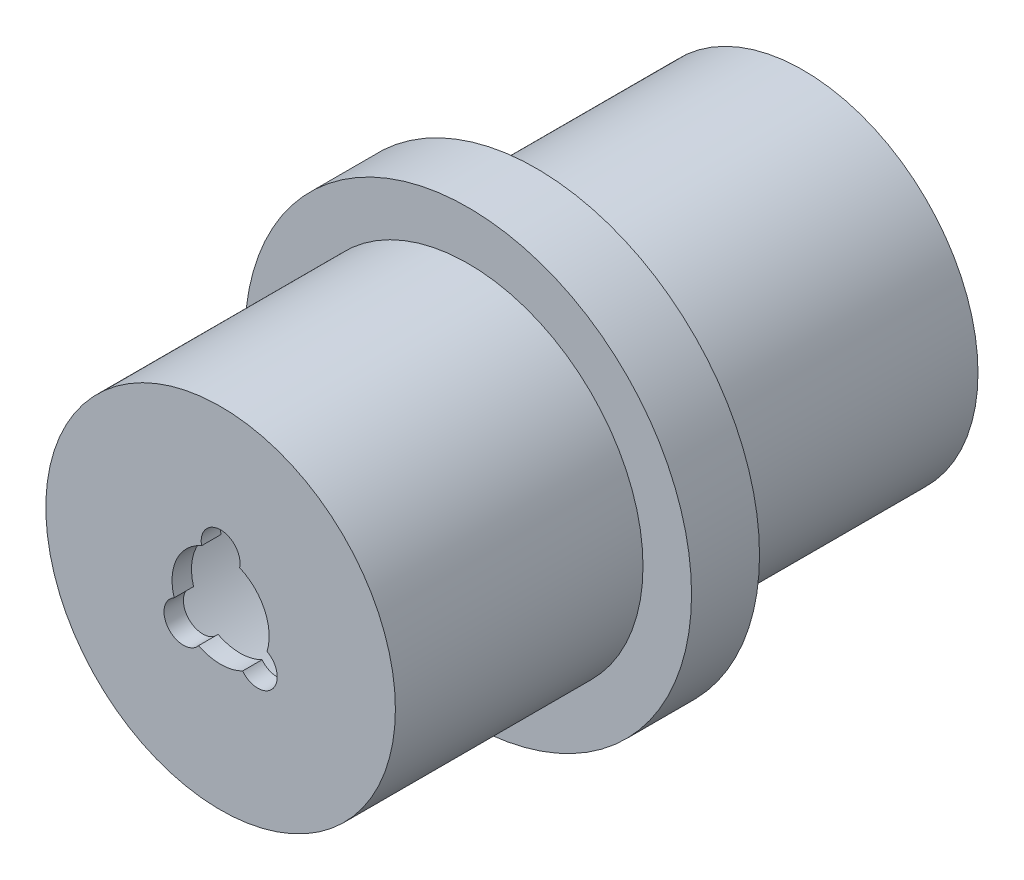
SolidWorks part; units mm, degrees
ref_plane "Front Plane" through (0, 0, 0) normal (0, 0, 1) x (1, 0, 0)
ref_plane "Top Plane" through (0, 0, 0) normal (0, 1, 0) x (1, 0, 0)
ref_plane "Right Plane" through (0, 0, 0) normal (1, 0, 0) x (0, 0, -1)
sketch "Sketch1" plane through (0, 0, 0) normal (1, 0, 0) x (0, 0, -1)
  line L0 (-60, 5) -> (-58, 5)
  line L1 (-60, 0) -> (0, 0)
  line L2 (-60, 0) -> (-60, 23)
  line L3 (-60, 23) -> (0, 23)
  line L4 (0, 0) -> (0, 23)
  line L5 (-1072.3815, 0) -> (1072.3815, 0) construction
  line L6 (-31, -974.342) -> (-31, 49025.6579)
  line L10 (-58, 0) -> (-2, 0)
  line L11 (-58, 0) -> (-58, 17)
  line L12 (-58, 17) -> (-2, 17)
  line L13 (-2, 0) -> (-2, 17)
  line L15 (-60, 18) -> (0, 18)
  line L16 (-27.5, 23) -> (-27.5, 18)
  line L17 (-2, 13) -> (0, 13)
  line L18 (-34.5, 23) -> (-34.5, 18)
  point P14 (-31, 17)
  dimension "D3" = 56
  dimension "D1" = 2
  dimension "D2" = 17
  dimension "D6" = 27
  dimension "D5" = 5
  dimension "D9" = 4
  dimension "D4" = 6
  dimension "D7" = 2
  dimension "D8" = 1
  dimension "D10" = 7
revolve "Revolve1" add sketch "Sketch1" angle 360 about L5 region at (0, 11.5, 59.6822) region at (0, 20.5, 32.75) region at (0, 17.5, 30.686) region at (0, 20.5, 29.25)
ref_axis "Axis1" through (0, 0, -68.4732) along (0, 0, 1)
ref_axis "Axis2" through (0, -974.342, 31) along (0, 1, 0)
ref_plane "Plane1" through (0, 0, 31) normal (0, 0, 1) x (1, 0, 0)
sketch "Sketch3" plane through (0, 0, 31) normal (0, 0, 1) x (1, 0, 0)
  line L0 (0, -999.5695) -> (0, 49000.4305) construction
  line L1 (-340.1578, -934.5758) -> (16760.8494, 46050.0552) construction
  line L2 (-1, 19.9725) -> (1, 19.9725)
  line L3 (338.8634, -931.0195) -> (-16762.1438, 46053.6116) construction
  line L4 (1, 19.9725) -> (4.5052, 16.5181) construction
  line L5 (0, 19.9725) -> (0, 23.1006) construction
  line L6 (2.0302, 19.9725) -> (-0.0328, 19.9725) construction
  line L7 (3.5107, 17.4982) -> (0.2868, 20.6753) construction
  line L8 (1, 19.9725) -> (1.1001, 21.9725) construction
  line L9 (4.5052, 16.5181) -> (4.684, 16.342)
  line L10 (6.4984, 17.8542) -> (7.5244, 20.6732)
  line L11 (-6.4984, 17.8542) -> (-7.5244, 20.6732)
  line L12 (-4.5052, 16.5181) -> (-4.684, 16.342)
  circle A4 centre (0, 0) radius 17 construction
  circle A6 centre (0, 0) radius 17
  circle A8 centre (5.2072, 17.2304) radius 1 construction
  arc A10 (6.4984, 17.8542) -> (-6.4984, 17.8542) centre (0, 0) cw
  circle A13 centre (0, 0) radius 22
  spline S0 degree 3 poles (1, 19.9725) (1.8375, 19.9725) (3.4007, 17.6066) (4.5052, 16.5181) knots 0 0 0 0 1 1 1 1
  spline S1 degree 3 poles (-1, 19.9725) (-1.8375, 19.9725) (-3.4007, 17.6066) (-4.5052, 16.5181) knots 0 0 0 0 1 1 1 1
  point P11 (0, 19.9725)
  point P13 (5.8143, 15.9748)
  point P16 (0, 22)
  point P20 (0, 19.9725)
  dimension "D2" = 2
  dimension "D4" = 20
  dimension "D1" = 5
  dimension "D3" = 1
  dimension "D5" = 2
  dimension "D6" = 2
extrude "Cut-Extrude1" cut sketch "Sketch3" against normal mid plane 4 contours L10 A13 L11 A10 S1 L2 S0 L9 A6 L12 region at (0, -18.441, 31)
extrude "Cut-Extrude2" cut sketch "Sketch3<5>" against normal mid plane 2 contours A6 | L2 S1 L12 A6 L9 S0 | L11 A13 L10 A10 region at (0, 18.1135, 31) region at (0, 0, 31) region at (7.5874, 19.0541, 31)
sketch "Sketch3<5>" plane through (0, 0, 31) normal (0, 0, 1) x (1, 0, 0) same geometry as "Sketch3"
ref_plane "Plane2" through (-7.5244, 20.6732, 32) normal (-0.9397, -0.342, 0) x (0, 0, 1)
sketch "Sketch5" plane through (0, 0, 60) normal (0, 0, 1) x (1, 0, 0)
  line L0 (3.8302, -3.2139) -> (-3.8302, -3.2139) construction
  circle A3 centre (0, 5) radius 2
  circle A4 centre (-3.8302, -3.2139) radius 2
  circle A5 centre (3.8302, -3.2139) radius 2
  circle A6 centre (0, 0) radius 5
  circle A7 centre (0, 0) radius 5 construction
  point P7 (0, -3.2139)
  circle M6 centre (0, 0) radius 5
extrude "Cut-Extrude3" cut sketch "Sketch5" against normal up to next contours A6 A4 M6 | A3 M6 | A6 A5 M6 region at (0, 5.7727, 60) region at (-4.4222, -3.7106, 60) region at (4.4222, -3.7106, 60)
equation "\"key_pin_length\"= 25.00mm"
equation "\"key_pin_dia\"= 20.00mm"
equation "\"driver_pin_travel\"= 3.00mm"
equation "\"driver_pin_dia\"= 0.3mm"
equation "\"plug_wall_thickness\" = 2mm"
equation "\"plug_spring_solid_length\"= 2mm"
equation "\"plug_length\"= 2 * \"key_pin_length\" + 2 * \"plug_wall_thickness\" + \"plug_spring_solid_length\""
equation "\"D3@Sketch1\"= \"plug_length\""
equation "\"D6@Sketch1\"= \"plug_wall_thickness\" + \"key_pin_length\""
equation "\"D7@Sketch1\"= \"D1@Sketch1\""
equation "\"driver_pin_head_dia\" = 2mm"
equation "\"D1@Sketch3\"=\"driver_pin_head_dia\"+\"driver_pin_travel\""
equation "\"true_gate_depth\" = 1.25mm"
equation "\"D4@Sketch1\"= \"driver_pin_head_dia\" + \"driver_pin_travel\" + 1mm"
equation "\"driver_pin_neck_dia\"= 2.00mm"
equation "\"driver_pin_head_length\" = 2mm"
equation "\"D1@Cut-Extrude1\"= \"driver_pin_neck_dia\" + \"driver_pin_head_length\""
equation "\"D1@Cut-Extrude2\"=\"driver_pin_neck_dia\""
equation "\"plug_dia\"= \"key_pin_dia\" + 2*(\"driver_pin_travel\" + 1mm + \"plug_spring_solid_length\" + 1mm)"
equation "\"D2@Sketch1\"=\"plug_dia\"/2"
equation "\"D2@Sketch3\"=\"driver_pin_head_dia\""
equation "\"D5@Sketch3\"=\"driver_pin_head_dia\""
equation "\"D6@Sketch3\"=\"driver_pin_head_dia\""
